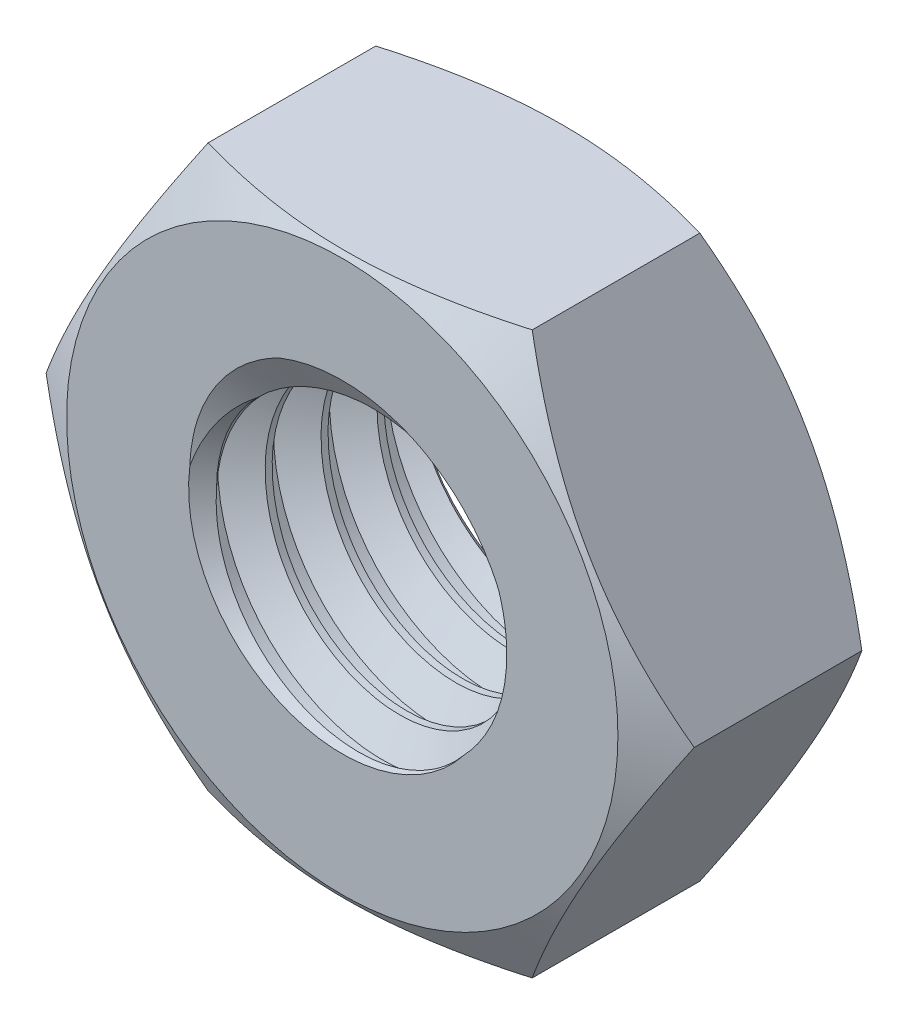
SolidWorks part; units mm, degrees
ref_plane "Front Plane" through (0, 0, 0) normal (0, 0, 1) x (1, 0, 0)
ref_plane "Top Plane" through (0, 0, 0) normal (0, 1, 0) x (1, 0, 0)
ref_plane "Right Plane" through (0, 0, 0) normal (1, 0, 0) x (0, 0, -1)
sketch "Sketch1" plane through (0, 0, 0) normal (1, 0, 0) x (0, 0, -1)
  line L0 (0, 0) -> (2, 0) construction
  line L1 (0, 1.375) -> (0.125, 1.25)
  line L2 (0.125, 1.25) -> (1.875, 1.25)
  line L3 (0, 1.375) -> (0, 2.467)
  line L4 (0.25, 2.9) -> (1.75, 2.9)
  line L5 (2, 1.375) -> (2, 2.467)
  line L6 (1.875, 1.25) -> (2, 1.375)
  line L7 (0, 2.467) -> (0.25, 2.9)
  line L8 (1.75, 2.9) -> (2, 2.467)
  point P3 (0, 1.25)
  point P4 (2, 2.9)
  point P5 (0, 2.9)
  point P6 (2, 1.25)
  point P15 (0, 0)
  dimension "D1" = 2
  dimension "D2" = 1.25
  dimension "D3" = 2.9
  dimension "D5" = 30
  dimension "D6" = 0.25
  dimension "D9" = 60
revolve "Revolve1" add sketch "Sketch1" angle 360 about L0
sketch "Sketch2" plane through (0, 0, 0) normal (0, 0, 1) x (1, 0, 0)
  line L1 (-1.45, 2.5115) -> (-2.9, 0)
  line L2 (-2.9, 0) -> (-1.45, -2.5115)
  line L3 (-1.45, -2.5115) -> (1.45, -2.5115)
  line L4 (1.45, -2.5115) -> (2.9, 0)
  line L5 (2.9, 0) -> (1.45, 2.5115)
  line L6 (1.45, 2.5115) -> (-1.45, 2.5115)
  circle A0 centre (0, 0) radius 2.9 construction
  circle A1 centre (0, 0) radius 2.9 construction
extrude "Cut-Extrude1" cut sketch "Sketch2" against normal up to next (2 mm away) flip side to cut
thread "Thread1" pitch 0.5 start angle 0, offset 1, length 0, pitch 0.5, diameter 2.5
ref_plane "Plane2" through (-1.25, 0, 0.875) normal (0, 1, 0) x (1, 0, 0)
sketch "Thread Profile2" plane through (-1.25, 0, 0.875) normal (0, 1, 0) x (1, 0, 0)
  line L0 (0, 0) -> (0, 0.5) construction
  line L11 (0, 0) -> (0, 0.4375)
  line L12 (0, 0.4375) -> (-0.2706, 0.2812)
  line L13 (-0.2706, 0.2812) -> (-0.2706, 0.1562)
  line L15 (-0.2706, 0.1562) -> (0, 0)
  line L17 (-0.2706, 0.2187) -> (0, 0.2187) construction
  point P2 (0, 0)
  dimension "Pitch" = 0.5
  dimension "Profile_Angle" = 60
  dimension "Profile_Land" = 0.125
  dimension "Profile_Height" = 0.2706
